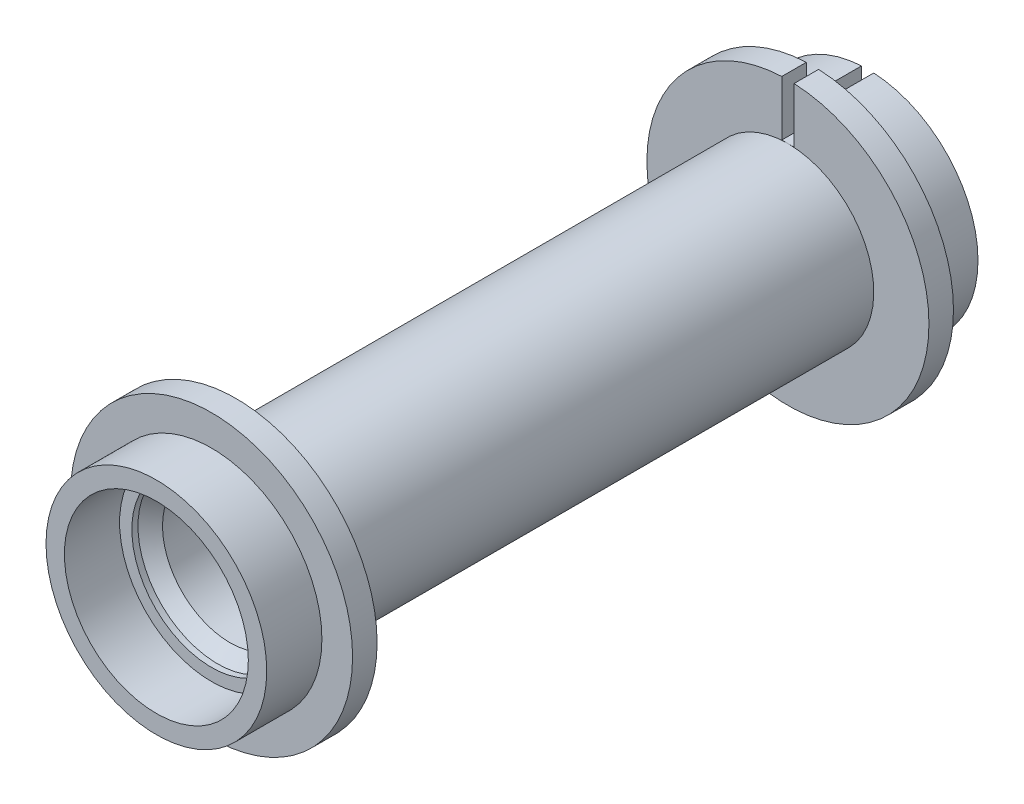
SolidWorks part; units mm, degrees
material "POM 乙缩醛共聚物"
ref_plane "前视基准面" through (0, 0, 0) normal (0, 0, 1) x (1, 0, 0)
ref_plane "上视基准面" through (0, 0, 0) normal (0, 1, 0) x (1, 0, 0)
ref_plane "右视基准面" through (0, 0, 0) normal (1, 0, 0) x (0, 0, -1)
sketch "草图1" plane through (0, 0, 0) normal (0, 0, 1) x (1, 0, 0)
  circle A0 centre (0, 0) radius 5.5
  circle A1 centre (0, 0) radius 7
  dimension "D1" = 14
  dimension "D2" = 11
extrude "凸台-拉伸1" add sketch "草图1" along normal blind 45
sketch "草图2" plane through (0, 0, 45) normal (0, 0, 1) x (1, 0, 0)
  circle A0 centre (0, 0) radius 6.5
  circle A1 centre (0, 0) radius 11.5
  dimension "D1" = 23
  dimension "D2" = 13
extrude "凸台-拉伸2" add sketch "草图2" along normal blind 2
sketch "草图3" plane through (0, 0, 47) normal (0, 0, 1) x (1, 0, 0)
  circle A0 centre (0, 0) radius 7.5
  circle A1 centre (0, 0) radius 9
  dimension "D1" = 15
  dimension "D2" = 18
extrude "凸台-拉伸3" add sketch "草图3" along normal blind 4.5
ref_plane "基准面2" through (0, 0, 22.5) normal (0, 0, -1) x (-1, 0, 0)
mirror "镜向16" about plane through (0, 0, 22.5) normal (0, 0, -1) of "凸台-拉伸3", "凸台-拉伸2"
chamfer "倒角1" distance 1.5 angle 45 2 edges at (6.5, 0, 45) (6.5, 0, 0)
sketch "草图5" plane through (0, 0, -6.5) normal (0, 0, -1) x (-1, 0, 0)
  line L0 (-0.5, 7) -> (0.5, 7)
  line L1 (-0.5, 7) -> (-0.5, 12.9564)
  line L2 (-0.5, 12.9564) -> (0.5, 12.9564)
  line L3 (0.5, 12.9564) -> (0.5, 7)
  point P0 (0, 7)
  point P3 (-10.5516, 6.2374)
  dimension "D1" = 7
  dimension "D2" = 1
extrude "切除-拉伸1" cut sketch "草图5" against normal up to surface (6.5 mm away) up to face at (-7, 0, 0)
